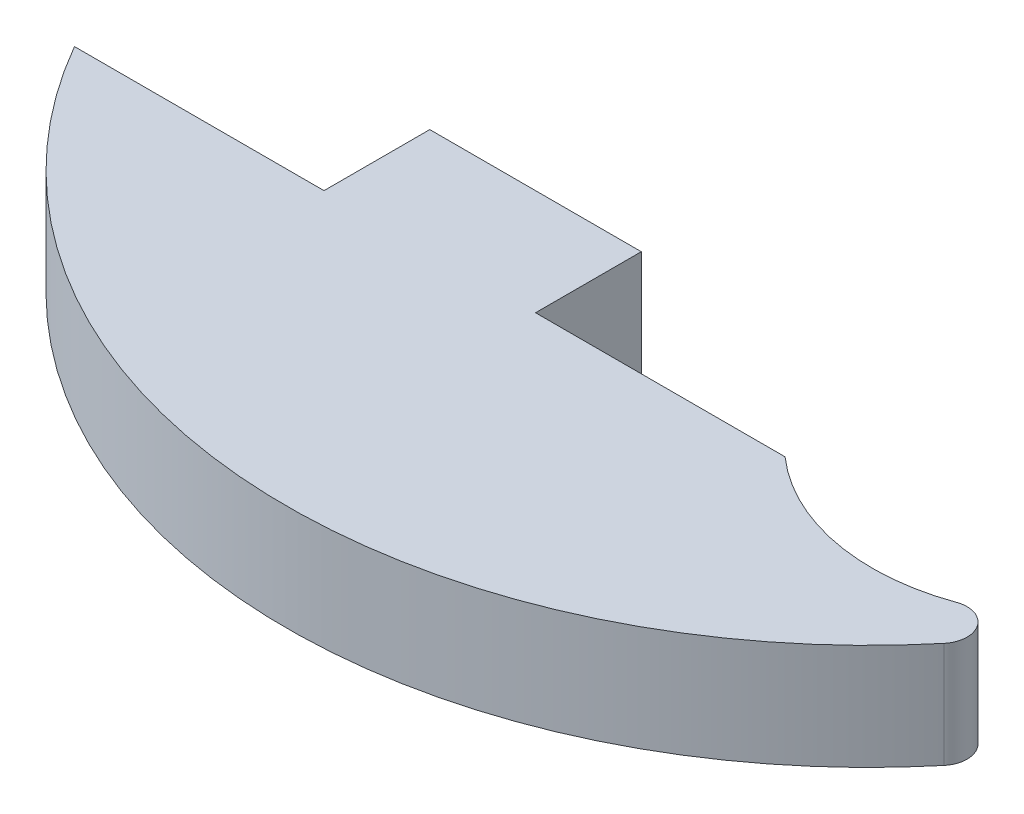
SolidWorks part; units mm, degrees
material "AISI 4130 Steel, annealed at 865C"
ref_plane "X-Y Datum" through (0, 0, 0) normal (0, 0, 1) x (1, 0, 0)
ref_plane "X-Z Datum" through (0, 0, 0) normal (0, 1, 0) x (1, 0, 0)
ref_plane "Y-Z Datum" through (0, 0, 0) normal (1, 0, 0) x (0, 0, -1)
sketch "Sketch1" plane through (0, 0, 0) normal (0, 1, 0) x (1, 0, 0)
  line L0 (-50.9024, -40.0059) -> (-57.5024, -40.0059) construction
  line L1 (-66.9024, -43.1809) -> (-24.236, -43.1809)
  line L2 (-54.2024, -41.3694) -> (-54.2024, -38.6423) construction
  line L5 (-41.5024, -43.1809) -> (-66.9024, -43.1809)
  line L6 (-54.2024, -43.1809) -> (-54.2024, -52.7059) construction
  line L7 (-66.9024, -36.8309) -> (-66.9024, -43.1809)
  arc A2 (-3.4102, -36.5946) -> (-66.9024, -43.1809) centre (-36.6195, -25.7827) cw
  circle A4 centre (-15.8357, -33.6559) radius 12.7
  point P2 (-24.497, -42.9442)
  point P3 (-54.2024, -40.0059)
  point P4 (0, 0)
  point P6 (-61.6586, -43.1809)
  point P10 (-63.864, -43.1809)
  point P11 (-15.8357, -44.7684)
  point P16 (-54.2024, -40.0059)
  point P20 (0, 0)
  point P21 (0, 0)
  point P22 (-15.8357, -32.0684)
  dimension "D1" = 34.925
extrude "Boss-Extrude1" add sketch "Sketch1" along normal mid plane 6.35 contours L1 L5 L6 region at (-37.6073, 0, 50.6496)
fillet "Fillet1" radius 1.5875 1 edges at (-3.9593, 0, 38.1548)
sketch "Sketch2" plane through (0, 3.175, 0) normal (0, 1, 0) x (1, 0, 0)
  line L0 (-66.9024, -43.1809) -> (-24.236, -43.1809) construction
  line L1 (-66.9024, -43.1809) -> (-24.236, -43.1809)
  line L2 (-45.5692, -43.1809) -> (-45.5692, -36.8309) construction
  line L8 (-39.2192, -43.1809) -> (-51.9192, -43.1809)
  line L9 (-39.2192, -43.1809) -> (-39.2192, -36.8309)
  line L10 (-39.2192, -36.8309) -> (-51.9192, -36.8309)
  line L11 (-51.9192, -43.1809) -> (-51.9192, -36.8309)
  line L12 (-39.2192, -43.1809) -> (-51.9192, -36.8309) construction
  line L13 (-39.2192, -36.8309) -> (-51.9192, -43.1809) construction
  point P2 (-45.5692, -40.0059)
  dimension "D1" = 6.35
  dimension "D2" = 12.7
extrude "Boss-Extrude2" add sketch "Sketch2" against normal blind 6.35 contours L11 L1 L9 L10 region at (-45.5692, 3.175, 40.0059)
